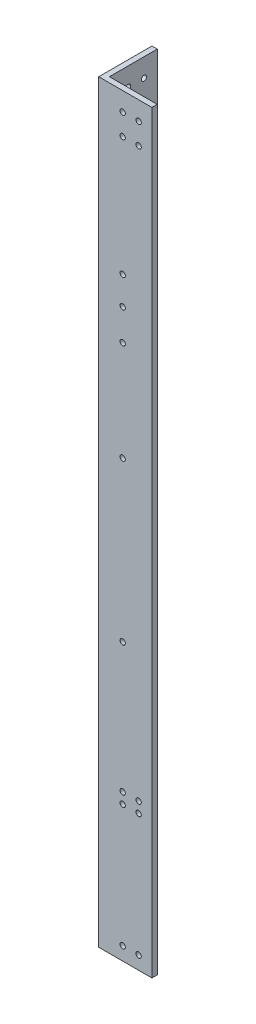
SolidWorks part; units mm, degrees
ref_plane "Front Plane" through (0, 0, 0) normal (0, 0, 1) x (1, 0, 0)
ref_plane "Top Plane" through (0, 0, 0) normal (0, 1, 0) x (1, 0, 0)
ref_plane "Right Plane" through (0, 0, 0) normal (1, 0, 0) x (0, 0, -1)
sketch "Sketch2" plane through (0, 0, 0) normal (0, 1, 0) x (1, 0, 0)
  line L0 (0, 31.75) -> (3.175, 31.75)
  line L1 (3.175, 31.75) -> (3.175, 3.175)
  line L2 (3.175, 3.175) -> (31.75, 3.175)
  line L3 (31.75, 3.175) -> (31.75, 0)
  line L4 (31.75, 0) -> (0, 0)
  line L5 (0, 0) -> (0, 31.75)
  point P9 (1.5875, 31.75)
  point P10 (31.75, 1.5875)
  dimension "D4" = 3.175
  dimension "D1" = 31.75
  dimension "D2" = 31.75
  dimension "D3" = 3.175
extrude "Boss-Extrude1" add sketch "Sketch2" along normal blind 450
sketch "FrontSideHoles-Sketch3" plane through (0, 0, 0) normal (0, 0, 1) x (1, 0, 0)
  line L0 (0, 0) -> (31.75, 0) construction
  line L3 (0, 450) -> (0, 0) construction
  circle A0 centre (14.2875, 81.1125) radius 1.5875
  circle A1 centre (23.8125, 81.1125) radius 1.5875
  circle A2 centre (14.2875, 87.4625) radius 1.5875
  circle A3 centre (23.8125, 87.4625) radius 1.5875
  circle A4 centre (14.2875, 438.8875) radius 1.5875
  circle A5 centre (14.2875, 426.1875) radius 1.5875
  circle A6 centre (23.8125, 438.8875) radius 1.5875
  circle A7 centre (23.8125, 426.1875) radius 1.5875
  circle A8 centre (14.2875, 338.1776) radius 1.5875
  circle A9 centre (14.2875, 319.6526) radius 1.5875
  circle A10 centre (14.2875, 260) radius 1.5875
  circle A11 centre (14.2875, 165) radius 1.5875
  circle A12 centre (14.2875, 355) radius 1.5875
  circle A13 centre (14.2875, 7.9375) radius 1.5875
  circle A14 centre (23.8125, 7.9375) radius 1.5875
  dimension "D4" = 3.175
  dimension "D1" = 81.1125
  dimension "D2" = 14.2875
  dimension "D8" = 11.1125
  dimension "D11" = 18.525
  dimension "D5" = 6.35
  dimension "D3" = 9.525
  dimension "D7" = 12.7
  dimension "D9" = 319.6526
  dimension "D6" = 165
  dimension "D10" = 95
  dimension "D13" = 95
  dimension "D12" = 7.9375
sketch "LeftSideHoles-Sketch4" plane through (0, 0, 0) normal (-1, 0, 0) x (0, 0, 1)
  line L0 (-31.75, 450) -> (0, 450) construction
  line L1 (0, 450) -> (0, 0) construction
  line L3 (-31.75, 0) -> (0, 0) construction
  circle A0 centre (-23.8125, 81.1125) radius 1.5875
  circle A1 centre (-14.2875, 81.1125) radius 1.5875
  circle A2 centre (-23.8125, 87.4625) radius 1.5875
  circle A3 centre (-14.2875, 87.4625) radius 1.5875
  circle A4 centre (-23.8125, 438.8875) radius 1.5875
  circle A5 centre (-14.2875, 438.8875) radius 1.5875
  circle A6 centre (-23.8125, 426.1875) radius 1.5875
  circle A7 centre (-14.2875, 426.1875) radius 1.5875
  circle A8 centre (-23.8125, 332.6026) radius 1.5875
  circle A9 centre (-14.2875, 332.6026) radius 1.5875
  circle A10 centre (-23.8125, 319.9026) radius 1.5875
  circle A11 centre (-14.2875, 319.9026) radius 1.5875
  circle A12 centre (-23.8125, 7.9375) radius 1.5875
  circle A13 centre (-14.2875, 7.9375) radius 1.5875
  dimension "D4" = 3.175
  dimension "D2" = 14.2875
  dimension "D7" = 12.7
  dimension "D3" = 81.1125
  dimension "D6" = 11.1125
  dimension "D5" = 6.35
  dimension "D10" = 7.9375
  dimension "D9" = 12.7
  dimension "D11" = 9.525
  dimension "D8" = 332.6026
extrude "FrontSideHoles-Cut-Extrude1" cut sketch "FrontSideHoles-Sketch3" against normal blind 3.175
extrude "LeftSideHoles-Cut-Extrude2" cut sketch "LeftSideHoles-Sketch4" against normal blind 3.175
equation "\"RailThickness\"= .125in'Spec"
equation "\"VSWidth\"= 1.25in'Spec"
equation "\"VSHeight\"= 1.25in'Spec"
equation "\"VSLength\"= 450mm"
equation "\"HoleOffsetFromEdge\"= \"RailThickness\" * 2.5"
equation "\"HoleOffsetFromSide\"= \"RailThickness\" * 3.5"
equation "\"LegHeight\"= 70mm'Space needed for PSU/Stepper/Electronics"
equation "\"VSBottomSideRailHoleY1FromBottomOfLowerRail\"= \"V1 BottomOfLowerRail\" + \"HoleOffsetFromSide\"'Equals 70.1125"
equation "\"VSSideRailHoleX1FromSide\"= \"HoleOffsetFromSide\" + \"RailThickness\""
equation "\"FasteningHoleDiameter\"= .125in"
equation "\"VSBottomSideRailHoleY2FromY1\"= \"LowerRailHeight\" - \"HoleOffsetFromSide\" - \"HoleOffsetFromEdge\"'Equals 6.35"
equation "\"VSTopSideRailHoleY1FromEdge\"= \"HoleOffsetFromEdge\" + \"RailThickness\""
equation "\"D4@FrontSideHoles-Sketch3\" = \"FasteningHoleDiameter\""
equation "\"D1@FrontSideHoles-Sketch3\" = \"VSBottomSideRailHoleY1FromBottomOfLowerRail\""
equation "\"D2@FrontSideHoles-Sketch3\" = \"VSSideRailHoleX1FromSide\""
equation "\"D1@Boss-Extrude1\"=\"VSLength\""
equation "\"D4@LeftSideHoles-Sketch4\" = \"FasteningHoleDiameter\""
equation "\"D3@LeftSideHoles-Sketch4\"= \"VSBottomSideRailHoleY1FromBottomOfLowerRail\""
equation "\"D2@LeftSideHoles-Sketch4\" = \"VSSideRailHoleX1FromSide\""
equation "\"D8@FrontSideHoles-Sketch3\" = \"VSTopSideRailHoleY1FromEdge\""
equation "\"D6@LeftSideHoles-Sketch4\" = \"VSTopSideRailHoleY1FromEdge\""
equation "\"VSMidSideRailHoleY1FromV8TopOfMidSideRail\"= \"V8 ToTopOfMidSideRail\" - \"HoleOffsetFromEdge\"'Equals 308.2875"
equation "\"LowerRailHeight\"= 1.00in"
equation "\"D1@Sketch2\"=\"VSHeight\""
equation "\"D2@Sketch2\"=\"VSWidth\""
equation "\"TopRailHeight\"= 1.25in"
equation "\"MidSideRailHeight\"= 1.25in"
equation "\"D5@LeftSideHoles-Sketch4\"=\"VSBottomSideRailHoleY2FromY1\""
equation "\"D5@FrontSideHoles-Sketch3\"=\"VSBottomSideRailHoleY2FromY1\""
equation "\"D10@LeftSideHoles-Sketch4\"=\"HoleOffsetFromEdge\""
equation "\"VSMidSideRailHoleY2FromY1\"= \"MidSideRailHeight\" - \"HoleOffsetFromSide\" - \"HoleOffsetFromEdge\"'Equals 12.7"
equation "\"D9@LeftSideHoles-Sketch4\"=\"VSMidSideRailHoleY2FromY1\""
equation "\"VSSideRailHoleX2FromX1\"= \"VSWidth\" - \"VSSideRailHoleX1FromSide\" - \"HoleOffsetFromEdge\""
equation "\"D3@FrontSideHoles-Sketch3\"=\"VSSideRailHoleX2FromX1\""
equation "\"D7@FrontSideHoles-Sketch3\"=\"VSMidSideRailHoleY2FromY1\""
equation "\"D11@LeftSideHoles-Sketch4\"=\"VSSideRailHoleX2FromX1\""
equation "\"VSTopSideRailHoleY2FromY1\"= \"TopRailHeight\" - \"VSTopSideRailHoleY1FromEdge\" - \"HoleOffsetFromEdge\"'Equals 12.7"
equation "\"D7@LeftSideHoles-Sketch4\"=\"VSTopSideRailHoleY2FromY1\""
equation "\"BeltTensionerInnerHeight\"= \"20TGT2PulleyWidth\" * 2 + \"1mmSpacer\" * 3"
equation "\"20TGT2PulleyWidth\"= 8.7mm'The STL of the Pulley in the diagram is a bit larger"
equation "\"1mmSpacer\"= 1mm"
equation "\"BeltTensionerHeight\"= \"BeltTensionerInnerHeight\" + \"BeltTensionerUpperLowerWallThickness\" * 2"
equation "\"BeltTensionerUpperLowerWallThickness\"= 7mm"
equation "\"D11@FrontSideHoles-Sketch3\"=\"VSBeltTensionerHoleY2FromY1\""
equation "\"VSBeltTensionerHoleY1FromBottom\"= \"V9 FromBottomGantryPulleyToBottomOfBeltTensioner\" + \"HoleOffsetFromEdge\""
equation "\"VSBeltTensionerHoleY2FromY1\"= \"BeltTensionerHeight\" - \"HoleOffsetFromEdge\" * 2"
equation "\"V1 BottomOfLowerRail\"= \"LegHeight\""
equation "\"StepperShaftLength\"= 24mm'Pulley will be attached to the end"
equation "\"ZAxisLeadScrewLength\"= 200mm"
equation "\"LM8UUHeight\"= 24mm'Spec"
equation "\"V2 ToBedAtTopOfZAxis\"= \"V1 BottomOfLowerRail\" + \"StepperShaftLength\" + \"ZAxisLeadScrewLength\" - \"LM8UUHeight\" / 2"
equation "\"HotEndToTopOfXAxisGB\"= 63.315144mm'Measured from the100.Should be 63.315144"
equation "\"TopOfGBToBottomOfLinearRail\"= \"LinearGBWidth\" / 2 + \"LinearRailWidth\" / 2"
equation "\"LinearGBWidth\"= 27mm'Spec"
equation "\"V5 ToBottomOfXAxisLinearRail\"= \"V4 ToTopOfBuildPlate/HotEndTip\" + \"HotEndToTopOfXAxisGB\" - \"TopOfGBToBottomOfLinearRail\""
equation "\"LinearRailWidth\"= 12mm'Spec"
equation "\"V6 ToBottomOfGantryPulley\"= \"V5 ToBottomOfXAxisLinearRail\" - \"DistanceFromGABTopToLowerPulley\""
equation "\"GABUpperHeight\"= 6mm"
equation "\"GABMidWallHeight\"= 28mm'Must equal 28 or changes alignment"
equation "\"GABMidShortRiserHeight\"= \"GABMidWallHeight\" / 2 - \"20TGT2PulleyWidth\"'Equals 5.3"
equation "\"GABRiserBossOffset\"= 0.8mm'Aligns Pulleys"
equation "\"DistanceFromGABTopToLowerPulley\"= \"GABUpperHeight\" + \"GABMidWallHeight\" - \"GABMidShortRiserHeight\" + \"GABRiserBossOffset\" / 2"
equation "\"V7 ToTopOfMidBackRail\"= \"V6 ToBottomOfGantryPulley\" + \"StepperShaftLength\""
equation "\"D8@LeftSideHoles-Sketch4\"= \"VSMidSideRailHoleY1FromV8TopOfMidSideRail\""
equation "\"BedToBuildPlateStandoffLength\"= 15mm"
equation "\"BuildPlateHeight\"= 8mm'Spec"
equation "\"V4 ToTopOfBuildPlate/HotEndTip\"= \"V2 ToBedAtTopOfZAxis\" + \"BedToBuildPlateStandoffLength\" + \"BuildPlateHeight\""
equation "\"D9@FrontSideHoles-Sketch3\"=\"VSBeltTensionerHoleY1FromBottom\""
equation "\"V8 ToTopOfMidSideRail\"= \"V7 ToTopOfMidBackRail\" - \"RailThickness\""
equation "\"V9 FromBottomGantryPulleyToBottomOfBeltTensioner\"= \"V6 ToBottomOfGantryPulley\" - \"BeltTensionerUpperLowerWallThickness\" - \"1mmSpacer\""
equation "\"BeltTensionerMountingHoleOffsetFromEdge\"= \"HoleOffsetFromEdge\""
equation "\"VSBeltTensionerXMountingHoleOffsetFromSide\"= \"BeltTensionerMountingHoleOffsetFromEdge\" + \"RailThickness\" * 2"
equation "\"VSEnclosureOffsets\"= ( \"VSLength\" - \"LegHeight\" ) / 4"
equation "\"D6@FrontSideHoles-Sketch3\"=\"LegHeight\" + \"VSEnclosureOffsets\""
equation "\"D10@FrontSideHoles-Sketch3\"=\"VSEnclosureOffsets\""
equation "\"D13@FrontSideHoles-Sketch3\"=\"VSEnclosureOffsets\""
equation "\"D12@FrontSideHoles-Sketch3\"=\"HoleOffsetFromEdge\""
